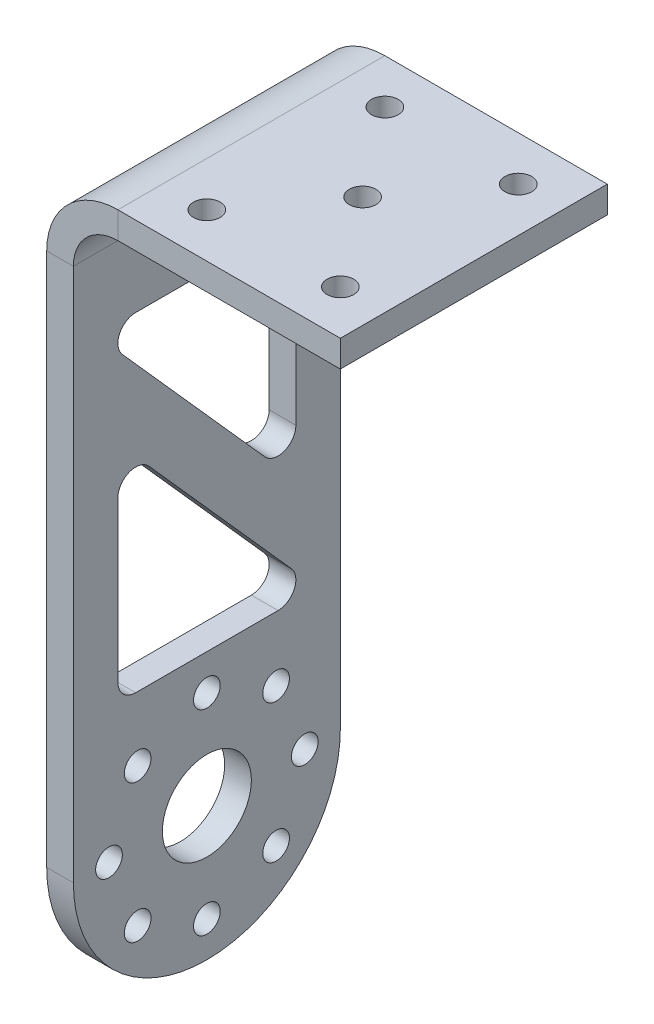
SolidWorks part; units mm, degrees
note: The reader was unsure of these and kept them because the rebuilt part matched: bend radius of "Basisbiegung1".
material "Alu Künz"
ref_plane "Ebene vorne" through (0, 0, 0) normal (0, 0, 1) x (1, 0, 0)
ref_plane "Ebene oben" through (0, 0, 0) normal (0, 1, 0) x (1, 0, 0)
ref_plane "Ebene rechts" through (0, 0, 0) normal (1, 0, 0) x (0, 0, -1)
sketch "Skizze1" plane through (0, 0, 0) normal (0, 0, 1) x (1, 0, 0)
  line L0 (0, -15) -> (0, 65)
  line L6 (0, 65) -> (30, 65)
  dimension "D1" = 15
  dimension "D2" = 30
  dimension "D5" = 80
sheet metal parameters "Blech1" thickness 3 parameters "D1"=5
base flange "Basis-Blech1" sketch "Skizze1" end condition mid plane depth 30 reverse direction no thickness 3 reverse thickness direction yes bend radius 5
bend "Basisbiegung1" bend radius 5 bend angle 90 parameters "D5"=1
sketch "Skizze2" plane through (0, 0, 0) normal (1, 0, 0) x (0, 0, -1)
  line L5 (-8, 52) -> (8, 52)
  line L6 (10, 50) -> (10, 32.0354)
  line L7 (6.5065, 30.7053) -> (-9.4935, 48.6698)
  line L8 (-6.5065, 36.2947) -> (9.4935, 18.3302)
  line L9 (8, 15) -> (-8, 15)
  line L10 (-10, 17) -> (-10, 34.9646)
  line L11 (15, -15) -> (15, 60) construction
  line L12 (-15, -15) -> (-15, 60) construction
  line L13 (-15, 60) -> (15, 60) construction
  circle A0 centre (0, 0) radius 5
  arc A1 (9.4935, 18.3302) -> (8, 15) centre (8, 17) cw
  arc A2 (-6.5065, 36.2947) -> (-10, 34.9646) centre (-8, 34.9646) ccw
  arc A3 (-8, 52) -> (-9.4935, 48.6698) centre (-8, 50) ccw
  arc A4 (10, 32.0354) -> (6.5065, 30.7053) centre (8, 32.0354) cw
  arc A5 (8, 52) -> (10, 50) centre (8, 50) cw
  arc A6 (-8, 15) -> (-10, 17) centre (-8, 17) cw
  dimension "D1" = 10
  dimension "D7" = 2
  dimension "D2" = 5
  dimension "D3" = 5
  dimension "D4" = 8
  dimension "D5" = 10
  dimension "D6" = 6
extrude "Schnitt-Linear austragen1" cut sketch "Skizze2" against normal through all both and the other way through all normal cut yes
fillet "Verrundung1" radius 15 2 edges at (-1.5, -15, -15) (-1.5, -15, 15)
sketch "Skizze4" plane through (0, 0, 0) normal (1, 0, 0) x (0, 0, -1)
  line L0 (0, 0) -> (0, 11) construction
  line L1 (0, 0) -> (7.7782, 7.7782) construction
  line L2 (0, 0) -> (11, 0) construction
  line L3 (0, 0) -> (7.7782, -7.7782) construction
  line L4 (0, 0) -> (0, -11) construction
  line L5 (0, 0) -> (-7.7782, -7.7782) construction
  line L6 (0, 0) -> (-11, 0) construction
  line L7 (0, 0) -> (-7.7782, 7.7782) construction
  point P12 (0, 0)
  dimension "D1" = 11
  dimension "D2" = 8
hole_wizard "Ø3.0 (3) Durchmesser Bohrung1" positions "Skizze5" profile "Skizze6" hole size "Ø3.0" standard "KUENZ_DIN" end condition through all
sketch "Skizze5" plane through (0, 0, 0) normal (1, 0, 0) x (0, 0, -1)
  point P0 (11, 0)
  point P3 (7.7782, 7.7782)
  point P6 (0, 11)
  point P9 (-7.7782, 7.7782)
  point P12 (-11, 0)
  point P15 (-7.7782, -7.7782)
  point P18 (0, -11)
  point P21 (7.7782, -7.7782)
sketch "Skizze6" plane through (0, 0, -11) normal (0, 1, 0) x (0, 0, -1)
  line L0 (0, 0) -> (0, 3)
  line L1 (0, 3) -> (1.5, 3)
  line L2 (1.5, 3) -> (1.5, 0)
  line L5 (1.5, 0) -> (0, 0)
  line L11 (0, -6.35) -> (0, 107.95) construction
  dimension "Bohrerdurchmesser" = 3
  dimension "Bohrungstiefe" = 3
sketch "Sketch1" plane through (0, 68, 0) normal (0, 1, 0) x (1, 0, 0)
  line L0 (10, -10) -> (25, 10) construction
  line L1 (10, 10) -> (25, 10) construction
  line L2 (10, 10) -> (10, -10) construction
  line L3 (10, -10) -> (25, -10) construction
  line L4 (25, 10) -> (25, -10) construction
  line L5 (0, 0) -> (17.5, 0) construction
  line L6 (30, -15) -> (30, 15) construction
  line L7 (5, 15) -> (30, 15) construction
  dimension "D1" = 5
  dimension "D2" = 5
  dimension "D3" = 15
hole_wizard "Ø3.0mm Dowel Hole1" positions "Sketch2" profile "Sketch3" hole size "Ø3.0" standard "ANSI Metric" end condition through all
sketch "Sketch2" plane through (0, 68, 0) normal (0, 1, 0) x (1, 0, 0)
  point P0 (10, 10)
  point P3 (25, 10)
  point P6 (17.5, 0)
  point P9 (10, -10)
  point P12 (25, -10)
sketch "Sketch3" plane through (10, 68, -10) normal (1, 0, 0) x (0, 0, 1)
  line L0 (0, 0) -> (0, 83)
  line L1 (0, 83) -> (1.5, 83)
  line L2 (1.5, 83) -> (1.5, 0)
  line L5 (1.5, 0) -> (0, 0)
  line L11 (0, -6.35) -> (0, 107.95) construction
  dimension "Thru Hole Dia." = 3
  dimension "Thru Hole Depth" = 83
flat pattern "Abwicklung1" [suppressed]
sketch "Biegung-Linien1" plane through (-47, 0, 0) normal (1, 0, 0) x (0, 0, -1)
  point P0 (-115, -2.8949)
  point P1 (115, -2.8949)
  point P2 (-115, 91.3153)
  point P3 (115, 91.3153)
sketch3d "Rahmen1" [suppressed]
  line L0 (230, 0, 0) -> (230, 388.4204, 0) construction
  line L1 (0, 0, 0) -> (0, 388.4204, 0) construction
  line L2 (230, 0, 0) -> (0, 0, 0) construction
  line L3 (230, 388.4204, 0) -> (0, 388.4204, 0) construction
bend of the flat pattern "Abwickeln-<Basisbiegung1>1"
